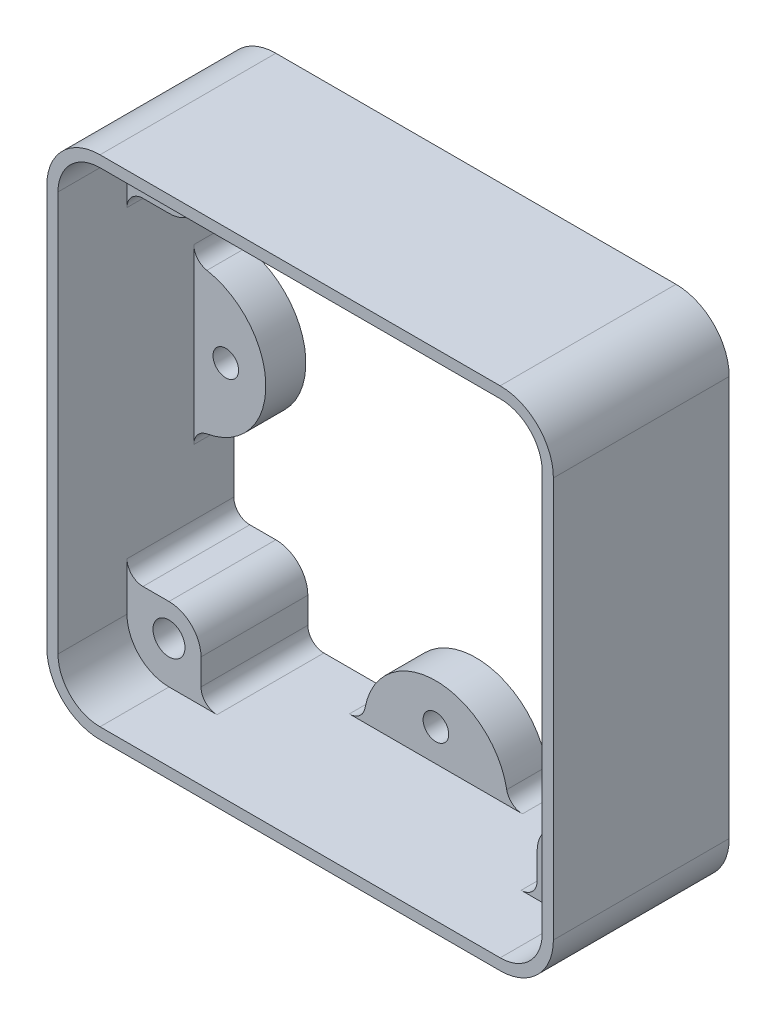
SolidWorks part; units mm, degrees
ref_plane "Front Plane" through (0, 0, 0) normal (0, 0, 1) x (1, 0, 0)
ref_plane "Top Plane" through (0, 0, 0) normal (0, 1, 0) x (1, 0, 0)
ref_plane "Right Plane" through (0, 0, 0) normal (1, 0, 0) x (0, 0, -1)
sketch "Sketch1" plane through (0, 0, 0) normal (0, 0, 1) x (1, 0, 0)
  line L0 (5, 60) -> (55, 60) construction
  line L1 (60, 55) -> (60, 5) construction
  line L2 (55, 0) -> (5, 0) construction
  line L3 (0, 5) -> (0, 55) construction
  line L4 (5, 60) -> (55, 60) construction
  line L5 (60, 55) -> (60, 5) construction
  line L6 (55, 0) -> (5, 0) construction
  line L7 (0, 5) -> (0, 55) construction
  line L8 (5, 60.25) -> (55, 60.25)
  line L9 (60.25, 55) -> (60.25, 5)
  line L10 (55, -0.25) -> (5, -0.25)
  line L11 (-0.25, 5) -> (-0.25, 55)
  line L12 (5.0003, 61.65) -> (54.9997, 61.65)
  line L13 (-1.65, 5.0003) -> (-1.65, 54.9997)
  line L14 (54.9997, -1.65) -> (5.0003, -1.65)
  line L15 (61.65, 54.9997) -> (61.65, 5.0003)
  circle A0 centre (5, 5) radius 1.6 construction
  circle A1 centre (55, 5) radius 1.6 construction
  circle A2 centre (55, 55) radius 1.6 construction
  circle A3 centre (5, 55) radius 1.6 construction
  arc A4 (60, 55) -> (55, 60) centre (55.0016, 55.0016) ccw construction
  arc A5 (55, 0) -> (60, 5) centre (55.0016, 4.9984) ccw construction
  arc A6 (0, 5) -> (5, 0) centre (4.9984, 4.9984) ccw construction
  arc A7 (5, 60) -> (0, 55) centre (4.9984, 55.0016) ccw construction
  circle A8 centre (5, 5) radius 1.6 construction
  circle A9 centre (55, 5) radius 1.6 construction
  circle A10 centre (55, 55) radius 1.6 construction
  circle A11 centre (5, 55) radius 1.6 construction
  arc A12 (60, 55) -> (55, 60) centre (55.0016, 55.0016) ccw construction
  arc A13 (55, 0) -> (60, 5) centre (55.0016, 4.9984) ccw construction
  arc A14 (0, 5) -> (5, 0) centre (4.9984, 4.9984) ccw construction
  arc A15 (5, 60) -> (0, 55) centre (4.9984, 55.0016) ccw construction
  arc A16 (60.25, 55) -> (55, 60.25) centre (55.0016, 55.0016) ccw
  arc A17 (55, -0.25) -> (60.25, 5) centre (55.0016, 4.9984) ccw
  arc A18 (-0.25, 5) -> (5, -0.25) centre (4.9984, 4.9984) ccw
  arc A19 (5, 60.25) -> (-0.25, 55) centre (4.9984, 55.0016) ccw
  arc A20 (61.65, 54.9997) -> (54.9997, 61.65) centre (55.0016, 55.0016) ccw
  arc A21 (5.0003, 61.65) -> (-1.65, 54.9997) centre (4.9984, 55.0016) ccw
  arc A22 (-1.65, 5.0003) -> (5.0003, -1.65) centre (4.9984, 4.9984) ccw
  arc A23 (54.9997, -1.65) -> (61.65, 5.0003) centre (55.0016, 4.9984) ccw
  circle A24 centre (5, 55) radius 2
  circle A25 centre (55, 55) radius 2
  circle A26 centre (55, 5) radius 2
  circle A27 centre (5, 5) radius 2
  dimension "D1" = 0.25
  dimension "D2" = 1.4
  dimension "D3" = 0.4
extrude "Boss-Extrude1" add sketch "Sketch1" along normal offset from surface 0.5 and the other way offset from surface (14.9702 mm away) 0.5 contours L14 A23 L15 A20 L12 A21 L13 A22 A19 L8 A16 L9 A17 L10 A18 L11
sketch "Sketch2" plane through (0, 0, 0) normal (0, 0, 1) x (1, 0, 0)
  line L0 (9, 55) -> (9, 60.25)
  line L1 (5, 60.25) -> (55, 60.25) construction
  line L2 (9, 60.25) -> (5, 60.25)
  line L3 (5, 51) -> (-0.25, 51)
  line L4 (-0.25, 5) -> (-0.25, 55) construction
  line L5 (-0.25, 51) -> (-0.25, 55)
  line L6 (30, 60) -> (30, 0) construction
  line L7 (60, 30) -> (0, 30) construction
  line L20 (51, 55) -> (51, 60.25)
  line L21 (55, 51) -> (60.25, 51)
  line L22 (60.25, 51) -> (60.25, 55)
  line L23 (51, 60.25) -> (55, 60.25)
  line L24 (55, 9) -> (60.25, 9)
  line L25 (51, 5) -> (51, -0.25)
  line L26 (51, -0.25) -> (55, -0.25)
  line L27 (60.25, 9) -> (60.25, 5)
  line L28 (9, 5) -> (9, -0.25)
  line L29 (5, 9) -> (-0.25, 9)
  line L30 (-0.25, 9) -> (-0.25, 5)
  line L31 (9, -0.25) -> (5, -0.25)
  arc A1 (5, 51) -> (9, 55) centre (5, 55) ccw
  circle A9 centre (5, 55) radius 2
  arc A12 (51, 55) -> (55, 51) centre (55, 55) ccw
  arc A13 (55, 9) -> (51, 5) centre (55, 5) ccw
  arc A14 (9, 5) -> (5, 9) centre (5, 5) ccw
  circle A15 centre (55, 55) radius 2
  circle A16 centre (55, 5) radius 2
  circle A17 centre (5, 5) radius 2
  spline S0 degree 3 poles (-0.25, 55) (-0.251, 58.0759) (1.9241, 60.251) (5, 60.25) knots 0 0 0 0 1 1 1 1 weights 1 0.804591 0.804591 1 construction
  spline S1 degree 3 poles (-0.25, 55) (-0.251, 58.0759) (1.9241, 60.251) (5, 60.25) knots 0 0 0 0 1 1 1 1 weights 1 0.804591 0.804591 1
  spline S3 degree 3 poles (55, 60.25) (58.0759, 60.251) (60.251, 58.0759) (60.25, 55) knots 0 0 0 0 1 1 1 1 weights 1 0.804591 0.804591 1
  spline S5 degree 3 poles (60.25, 5) (60.251, 1.9241) (58.0759, -0.251) (55, -0.25) knots 0 0 0 0 1 1 1 1 weights 1 0.804591 0.804591 1
  spline S7 degree 3 poles (5, -0.25) (1.9241, -0.251) (-0.251, 1.9241) (-0.25, 5) knots 0 0 0 0 1 1 1 1 weights 1 0.804591 0.804591 1
  point P6 (0, 0)
  point P10 (0, 0)
  point P12 (0, 0)
  point P13 (30, 30)
  point P20 (0, 0)
  point P42 (30, 30)
  point P46 (30, 30)
  point P50 (30, 30)
  point P52 (0, 0)
  dimension "D4" = 4
  dimension "D1" = 4
  dimension "D2" = 4
  dimension "D3" = 4
extrude "Boss-Extrude2" add sketch "Sketch2" along normal up to surface (13.3508 mm away) from surface at -14.9702 starting at face at (30, 30, -14.9702)
sketch "Sketch3" plane through (0, 0, 0) normal (0, 0, 1) x (1, 0, 0)
  line L0 (60.25, 21) -> (60.25, 39)
  line L1 (39, 60.25) -> (21, 60.25)
  line L5 (21, -0.25) -> (39, -0.25)
  line L6 (55, 60.25) -> (5, 60.25) construction
  line L7 (-0.25, 39) -> (-0.25, 21)
  arc A0 (21, 60.25) -> (39, 60.25) centre (30, 60.25) ccw
  circle A1 centre (30, 56.25) radius 1.6
  arc A2 (60.25, 39) -> (60.25, 21) centre (60.25, 30) ccw
  circle A3 centre (56.25, 30) radius 1.6
  arc A4 (39, -0.25) -> (21, -0.25) centre (30, -0.25) ccw
  circle A5 centre (30, 3.75) radius 1.6
  arc A6 (-0.25, 21) -> (-0.25, 39) centre (-0.25, 30) ccw
  circle A7 centre (3.75, 30) radius 1.6
  point P9 (30, 60.25)
  point P10 (30, 30)
  point P27 (30, 30)
  dimension "D1" = 9
  dimension "D2" = 4
  dimension "D3" = 3.2
  dimension "D4" = 4
extrude "Boss-Extrude3" add sketch "Sketch3" along normal blind 5 from surface
fillet "Fillet1" radius 2 16 edges at (-0.25, 39, -12.4702) (-0.25, 21, -12.4702) (21, -0.25, -12.4702) (39, -0.25, -12.4702) (60.25, 21, -12.4702) (60.25, 39, -12.4702) (39, 60.25, -12.4702) (21, 60.25, -12.4702) (-0.25, 9, -8.2948) (9, -0.25, -8.2948) (51, -0.25, -8.2948) (60.25, 9, -8.2948) (60.25, 51, -8.2948) (51, 60.25, -8.2948) (9, 60.25, -8.2948) (-0.25, 51, -8.2948)
